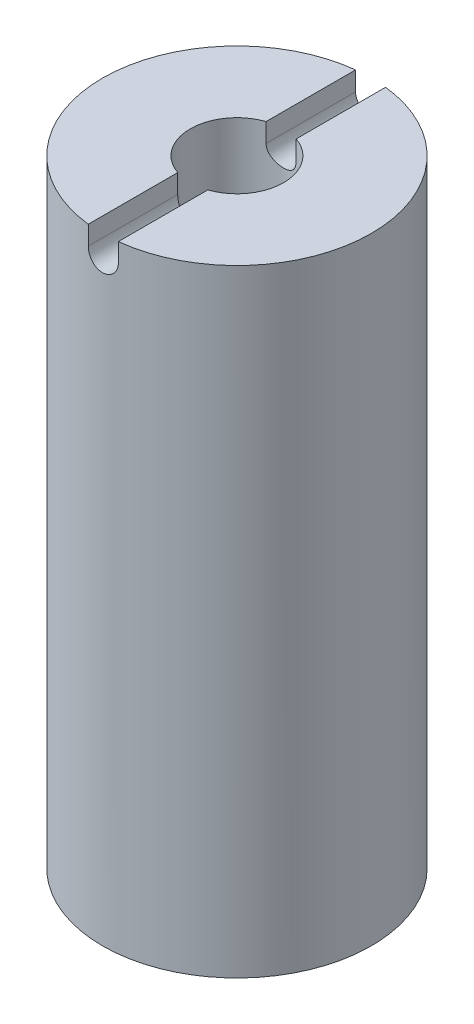
SolidWorks part; units mm, degrees
ref_plane "Front Plane" through (0, 0, 0) normal (0, 0, 1) x (1, 0, 0)
ref_plane "Top Plane" through (0, 0, 0) normal (0, 1, 0) x (1, 0, 0)
ref_plane "Right Plane" through (0, 0, 0) normal (1, 0, 0) x (0, 0, -1)
sketch "Sketch1" plane through (0, 0, 0) normal (0, 1, 0) x (1, 0, 0)
  arc A0 (-0.9436, 4.9102) -> (-2.4334, 4.3679) centre (0, 0) ccw
  arc A1 (-0.7151, 4.774) -> (0.7151, 4.774) centre (0, 5) ccw
  arc A2 (0.7151, 4.774) -> (0.9436, 4.9102) centre (0.9058, 4.7138) cw
  arc A3 (-0.7151, 4.774) -> (-0.9436, 4.9102) centre (-0.9058, 4.7138) ccw
  arc A4 (2.5208, 4.1168) -> (3.6165, 3.1974) centre (3.2139, 3.8302) ccw
  arc A5 (3.6165, 3.1974) -> (3.879, 3.1549) centre (3.7239, 3.0287) cw
  arc A6 (2.5208, 4.1168) -> (2.4334, 4.3679) centre (2.336, 4.1932) ccw
  arc A7 (4.5773, 1.5333) -> (4.8257, 0.1247) centre (4.924, 0.8682) ccw
  arc A8 (4.8257, 0.1247) -> (4.9994, -0.0766) centre (4.7994, -0.0736) cw
  arc A9 (4.5773, 1.5333) -> (4.6717, 1.7819) centre (4.4848, 1.7106) ccw
  arc A10 (4.492, -1.7677) -> (3.7768, -3.0063) centre (4.3301, -2.5) ccw
  arc A11 (3.7768, -3.0063) -> (3.7805, -3.2723) centre (3.6293, -3.1414) cw
  arc A12 (4.492, -1.7677) -> (4.7241, -1.6379) centre (4.5352, -1.5724) ccw
  arc A13 (2.3048, -4.2415) -> (0.9608, -4.7307) centre (1.7101, -4.6985) ccw
  arc A14 (0.9608, -4.7307) -> (0.7927, -4.9368) centre (0.761, -4.7393) cw
  arc A15 (2.3048, -4.2415) -> (2.5661, -4.2913) centre (2.4634, -4.1197) ccw
  arc A16 (-0.9608, -4.7307) -> (-2.3048, -4.2415) centre (-1.7101, -4.6985) ccw
  arc A17 (-2.3048, -4.2415) -> (-2.5661, -4.2913) centre (-2.4634, -4.1197) cw
  arc A18 (-0.9608, -4.7307) -> (-0.7927, -4.9368) centre (-0.761, -4.7393) ccw
  arc A19 (-3.7768, -3.0063) -> (-4.492, -1.7677) centre (-4.3301, -2.5) ccw
  arc A20 (-4.492, -1.7677) -> (-4.7241, -1.6379) centre (-4.5352, -1.5724) cw
  arc A21 (-3.7768, -3.0063) -> (-3.7805, -3.2723) centre (-3.6293, -3.1414) ccw
  arc A22 (-4.8257, 0.1247) -> (-4.5773, 1.5333) centre (-4.924, 0.8682) ccw
  arc A23 (-4.5773, 1.5333) -> (-4.6717, 1.7819) centre (-4.4848, 1.7106) cw
  arc A24 (-4.8257, 0.1247) -> (-4.9994, -0.0766) centre (-4.7994, -0.0736) ccw
  arc A25 (-3.6165, 3.1974) -> (-2.5208, 4.1168) centre (-3.2139, 3.8302) ccw
  arc A26 (-2.5208, 4.1168) -> (-2.4334, 4.3679) centre (-2.336, 4.1932) cw
  arc A27 (-3.6165, 3.1974) -> (-3.879, 3.1549) centre (-3.7239, 3.0287) ccw
  arc A28 (-3.879, 3.1549) -> (-4.6717, 1.7819) centre (0, 0) ccw
  arc A29 (-4.9994, -0.0766) -> (-4.7241, -1.6379) centre (0, 0) ccw
  arc A30 (-3.7805, -3.2723) -> (-2.5661, -4.2913) centre (0, 0) ccw
  arc A31 (-0.7927, -4.9368) -> (0.7927, -4.9368) centre (0, 0) ccw
  arc A32 (2.5661, -4.2913) -> (3.7805, -3.2723) centre (0, 0) ccw
  arc A33 (4.7241, -1.6379) -> (4.9994, -0.0766) centre (0, 0) ccw
  arc A34 (4.6717, 1.7819) -> (3.879, 3.1549) centre (0, 0) ccw
  arc A35 (2.4334, 4.3679) -> (0.9436, 4.9102) centre (0, 0) ccw
  circle A36 centre (0, 0) radius 8.5
  arc A37 (5.5495, 0.1434) -> (5.7493, -0.0881) centre (5.5194, -0.0846) cw
  arc A38 (2.6505, -4.8777) -> (1.1049, -5.4403) centre (1.9666, -5.4032) ccw
  arc A39 (-0.8224, 5.4901) -> (0.8224, 5.4901) centre (0, 5.75) ccw
  arc A40 (-5.1658, -2.0328) -> (-5.4327, -1.8836) centre (-5.2154, -1.8082) cw
  arc A41 (-5.7493, -0.0881) -> (-5.4327, -1.8836) centre (0, 0) ccw
  arc A42 (5.2639, 1.7633) -> (5.3725, 2.0492) centre (5.1576, 1.9672) ccw
  arc A43 (2.951, -4.935) -> (4.3476, -3.7631) centre (0, 0) ccw
  arc A44 (-1.0851, 5.6467) -> (-2.7984, 5.0231) centre (0, 0) ccw
  arc A45 (4.3434, -3.4573) -> (4.3476, -3.7631) centre (4.1737, -3.6126) cw
  arc A46 (2.7984, 5.0231) -> (1.0851, 5.6467) centre (0, 0) ccw
  arc A47 (1.1049, -5.4403) -> (0.9116, -5.6773) centre (0.8751, -5.4502) cw
  arc A48 (2.899, 4.7343) -> (4.159, 3.677) centre (3.696, 4.4048) ccw
  arc A49 (-4.3434, -3.4573) -> (-4.3476, -3.7631) centre (-4.1737, -3.6126) ccw
  arc A50 (5.2639, 1.7633) -> (5.5495, 0.1434) centre (5.6626, 0.9985) ccw
  arc A51 (-5.5495, 0.1434) -> (-5.7493, -0.0881) centre (-5.5194, -0.0846) ccw
  arc A52 (-4.159, 3.677) -> (-2.899, 4.7343) centre (-3.696, 4.4048) ccw
  arc A53 (-4.3434, -3.4573) -> (-5.1658, -2.0328) centre (-4.9796, -2.875) ccw
  arc A54 (4.159, 3.677) -> (4.4609, 3.6281) centre (4.2824, 3.483) cw
  arc A55 (-5.2639, 1.7633) -> (-5.3725, 2.0492) centre (-5.1576, 1.9672) cw
  arc A56 (-4.159, 3.677) -> (-4.4609, 3.6281) centre (-4.2824, 3.483) ccw
  arc A57 (-2.6505, -4.8777) -> (-2.951, -4.935) centre (-2.8329, -4.7376) cw
  arc A58 (5.4327, -1.8836) -> (5.7493, -0.0881) centre (0, 0) ccw
  arc A59 (5.1658, -2.0328) -> (4.3434, -3.4573) centre (4.9796, -2.875) ccw
  arc A60 (5.3725, 2.0492) -> (4.4609, 3.6281) centre (0, 0) ccw
  arc A61 (-0.8224, 5.4901) -> (-1.0851, 5.6467) centre (-1.0417, 5.4208) ccw
  arc A62 (5.1658, -2.0328) -> (5.4327, -1.8836) centre (5.2154, -1.8082) ccw
  arc A63 (-4.3476, -3.7631) -> (-2.951, -4.935) centre (0, 0) ccw
  arc A64 (0.8224, 5.4901) -> (1.0851, 5.6467) centre (1.0417, 5.4208) cw
  arc A65 (-1.1049, -5.4403) -> (-0.9116, -5.6773) centre (-0.8751, -5.4502) ccw
  arc A66 (-0.9116, -5.6773) -> (0.9116, -5.6773) centre (0, 0) ccw
  arc A67 (2.899, 4.7343) -> (2.7984, 5.0231) centre (2.6864, 4.8222) ccw
  arc A68 (-5.5495, 0.1434) -> (-5.2639, 1.7633) centre (-5.6626, 0.9985) ccw
  arc A69 (2.6505, -4.8777) -> (2.951, -4.935) centre (2.8329, -4.7376) ccw
  arc A70 (-2.899, 4.7343) -> (-2.7984, 5.0231) centre (-2.6864, 4.8222) cw
  arc A71 (-1.1049, -5.4403) -> (-2.6505, -4.8777) centre (-1.9666, -5.4032) ccw
  arc A72 (-4.4609, 3.6281) -> (-5.3725, 2.0492) centre (0, 0) ccw
  point P67 (0, 0)
  point P131 (0, 0)
  point P132 (0, 0)
  point P133 (0, 0)
  point P134 (0, 0)
  point P135 (0, 0)
  point P136 (0, 0)
  point P137 (0, 0)
  dimension "D1" = 10
  dimension "D2" = 1.5
  dimension "D3" = 0.2
  dimension "D5" = 17
  dimension "D4" = 9
extrude "Boss-Extrude1" add sketch "Sketch1" along normal blind 29 contours A36 A51 A68 A55 A72 A56 A52 A70 A44 A61 A39 A64 A46 A67 A48 A54 A60 A42 A50 A37 A58 A62 A59 A45 A43 A69 A38 A47 A66 A65 A71 A57 A63 A49 A53 A40 A41 region at (-8.2596, 0, 0)
sketch "Sketch2" plane through (0, 0, 0) normal (0, 0, 1) x (1, 0, 0)
  line L2 (-8.5, 39) -> (-2.95, 39)
  line L3 (0, 0) -> (0, 26.0538) construction
  line L4 (-8.5, 29) -> (-2.95, 29)
  line L7 (0.8224, 29) -> (-0.8224, 29) construction
  line L8 (0, 26.0538) -> (0, 29)
  line L10 (-8.5, 29) -> (-8.5, 39)
  line L11 (-2.95, 39) -> (-2.95, 29)
  dimension "D1" = 10
  dimension "D2" = 5.9
revolve "Revolve2" add sketch "Sketch2" angle 360 about L3 region at (-5.725, 34, 0)
sketch "Sketch4" plane through (0, 0, 0) normal (0, 0, 1) x (1, 0, 0)
  line L0 (0, 39) -> (0, 37.8) construction
  line L1 (8.5, 39) -> (-8.5, 39) construction
  line L2 (0, 39) -> (0, 0) construction
  line L3 (-0.95, 37.8) -> (-0.95, 39)
  line L4 (2.95, 39) -> (-2.95, 39) construction
  line L5 (-0.95, 39) -> (0.95, 39)
  line L6 (0.95, 39) -> (0.95, 37.8)
  arc A0 (-0.95, 37.8) -> (0.95, 37.8) centre (0, 37.8) ccw
  dimension "D1" = 1.9
  dimension "D2" = 1.2
extrude "Cut-Extrude1" cut sketch "Sketch4" against normal blind 10 and the other way blind 10
